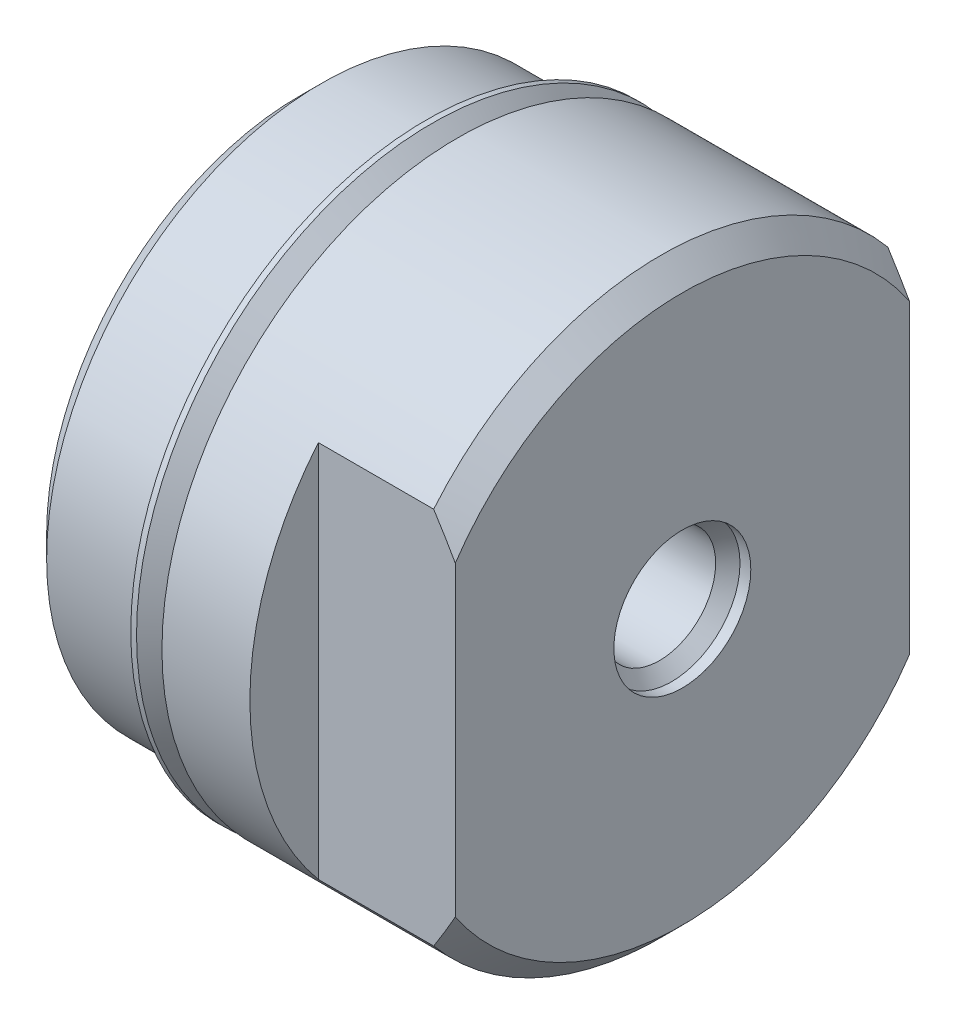
SolidWorks part; units mm, degrees
material "AISI 304"
ref_plane "Front Plane" through (0, 0, 0) normal (0, 0, 1) x (1, 0, 0)
ref_plane "Top Plane" through (0, 0, 0) normal (0, 1, 0) x (1, 0, 0)
ref_plane "Right Plane" through (0, 0, 0) normal (1, 0, 0) x (0, 0, -1)
sketch "Sketch1" plane through (0, 0, 0) normal (0, 0, 1) x (1, 0, 0)
  line L0 (0, 0) -> (0, 8.9154)
  line L1 (0, 8.9154) -> (0.762, 9.6774)
  line L2 (0.762, 9.6774) -> (4.0386, 9.6774)
  line L3 (4.0386, 9.6774) -> (4.8006, 8.9154)
  line L4 (4.8006, 8.9154) -> (5.5626, 8.9154)
  line L5 (5.5626, 8.9154) -> (5.5626, 10.414)
  line L6 (5.5626, 10.414) -> (12.7254, 10.414)
  line L7 (12.7254, 10.414) -> (13.4874, 9.652)
  line L8 (13.4874, 9.652) -> (13.4874, 0)
  line L9 (13.4874, 0) -> (0, 0)
  line L10 (13.4874, 0) -> (0, 0) construction
revolve "Revolve1" add sketch "Sketch1" angle 360 about L10 reverse direction yes
ref_plane "Plane1" through (13.4874, 0, 0) normal (1, 0, 0) x (0, 0, -1)
sketch "Sketch2" plane through (13.4874, 0, 0) normal (1, 0, 0) x (0, 0, -1)
  line L0 (-16.002, -41.656) -> (16.002, -41.656)
  line L1 (16.002, -41.656) -> (16.002, 41.656)
  line L2 (16.002, 41.656) -> (-16.002, 41.656)
  line L3 (-16.002, 41.656) -> (-16.002, -41.656)
  line L4 (-8.001, -20.828) -> (8.001, -20.828)
  line L5 (8.001, -20.828) -> (8.001, 20.828)
  line L6 (8.001, 20.828) -> (-8.001, 20.828)
  line L7 (-8.001, 20.828) -> (-8.001, -20.828)
extrude "Cut-Extrude1" cut sketch "Sketch2" against normal blind 4.826
hole_wizard "Hole1" positions "Sketch4" profile "Sketch3" legacy
sketch "Sketch4" plane through (0, 0, 0) normal (-1, 0, 0) x (0, 0, 1)
  point P0 (0, 0)
sketch "Sketch3" plane through (0, 0, 0) normal (0, 1, 0) x (0, 0, 1)
  line L0 (0, 0) -> (0, 6.35)
  line L1 (0, 6.35) -> (6.35, 6.35)
  line L2 (6.35, 6.35) -> (6.35, 0.254)
  line L3 (6.35, 0.254) -> (6.604, 0)
  line L4 (6.604, 0) -> (0, 0)
  line L5 (0, -6.4453) -> (0, 115.525) construction
  line L6 (-6.35, 0.254) -> (-6.604, 0) construction
  dimension "Diameter" = 12.7
  dimension "Depth" = 6.35
  dimension "C-Sink Angle" = 90
  dimension "C-Sink Diameter" = 13.208
hole_wizard "Hole2" positions "Sketch6" profile "Sketch5" legacy
sketch "Sketch6" plane through (13.4874, 0, 0) normal (1, 0, 0) x (0, 0, -1)
  point P0 (0, 0)
sketch "Sketch5" plane through (13.4874, 0, 0) normal (0, 1, 0) x (0, 0, -1)
  line L0 (0, 0) -> (0, 13.8684)
  line L1 (0, 13.8684) -> (1.9837, 13.8684)
  line L2 (1.9837, 13.8684) -> (1.9837, 0.8103)
  line L3 (1.9837, 0.8103) -> (2.413, 0.381)
  line L4 (2.413, 0.381) -> (2.413, 0)
  line L5 (2.413, 0) -> (0, 0)
  line L6 (0, -6.13) -> (0, 109.2824) construction
  line L7 (-1.9837, 0.8103) -> (-2.413, 0.381) construction
  line L8 (0, 13.8684) -> (-1.9837, 13.8684) construction
  dimension "Diameter" = 3.9675
  dimension "Depth" = 13.8684
  dimension "C-Drill Diameter" = 4.826
  dimension "C-Drill Depth" = 0.381
  dimension "C-Drill Angle" = 90
cosmetic thread "Cosmetic Thread1" parameters "D1"=7.1374, "D2"=4.826
sketch "Sketch7" plane through (0, 0, 0) normal (0, 0, 1) x (1, 0, 0)
  line L0 (4.4638, 10.3298) -> (5.8782, 8.9154)
  line L1 (5.8782, 8.9154) -> (6.1656, 8.9154)
  line L2 (6.1656, 8.9154) -> (4.667, 10.414)
  line L3 (4.667, 10.414) -> (4.4638, 10.414)
  line L4 (4.4638, 10.414) -> (4.4638, 10.3298)
  line L5 (13.4874, 0) -> (-13.4874, 0) construction
revolve "Revolve2" add sketch "Sketch7" angle 360 about L5 reverse direction yes
ref_plane "Plane2" through (13.4874, 0, 0) normal (1, 0, 0) x (0, 0, -1)
ref_plane "Plane3" through (4.0386, 0, 0) normal (1, 0, 0) x (0, 0, -1)
ref_plane "Plane4" through (0, 0, 0) normal (0, 1, 0) x (1, 0, 0)
ref_plane "Plane5" through (0, 0, 0) normal (0, 0, 1) x (1, 0, 0)
ref_plane "Plane6" through (0, 0, 0) normal (0, 0, 1) x (1, 0, 0)
ref_plane "Plane7" through (0, 0, 0) normal (0, 1, 0) x (1, 0, 0)
ref_plane "Plane8" through (13.4874, 0, 0) normal (1, 0, 0) x (0, 0, -1)
ref_plane "Plane9" through (13.4874, 0, 0) normal (1, 0, 0) x (0, 0, -1)
ref_plane "Plane10" through (13.4874, 0, 0) normal (1, 0, 0) x (0, 0, -1)
ref_plane "a1 XY" through (0, 0, 0) normal (0, 1, 0) x (1, 0, 0)
ref_plane "a1 XZ" through (0, 0, -10.414) normal (0, 0, 1) x (1, 0, 0)
ref_plane "a1 YZ" through (13.4874, 0, 0) normal (1, 0, 0) x (0, 0, -1)
ref_axis "a1 X" through (-80.9, 0, -10.414) along (1, 0, 0)
ref_axis "a1 Y" through (13.4874, 0, 50) along (0, 0, -1)
ref_axis "a1 Z" through (13.4874, 50, -10.414) along (0, -1, 0)
sketch3d "a1"
  point P0 (13.4874, 0, -10.414)
ref_plane "a2 XY" through (0, 0, 0) normal (0, 1, 0) x (1, 0, 0)
ref_plane "a2 XZ" through (0, 0, 10.414) normal (0, 0, 1) x (1, 0, 0)
ref_plane "a2 YZ" through (13.4874, 0, 0) normal (1, 0, 0) x (0, 0, -1)
ref_axis "a2 X" through (-80.9, 0, 10.414) along (1, 0, 0)
ref_axis "a2 Y" through (13.4874, 0, 50) along (0, 0, -1)
ref_axis "a2 Z" through (13.4874, 50, 10.414) along (0, -1, 0)
sketch3d "a2"
  point P0 (13.4874, 0, 10.414)
ref_plane "aa2 XY" through (0, 0, 0) normal (0, 1, 0) x (1, 0, 0)
ref_plane "aa2 XZ" through (0, 0, 0) normal (0, 0, 1) x (1, 0, 0)
ref_plane "aa2 YZ" through (13.4874, 0, 0) normal (1, 0, 0) x (0, 0, -1)
ref_axis "aa2 X" through (-80.9, 0, 0) along (1, 0, 0)
ref_axis "aa2 Y" through (13.4874, 0, 50) along (0, 0, -1)
ref_axis "aa2 Z" through (13.4874, 50, 0) along (0, -1, 0)
sketch3d "aa2"
  point P0 (13.4874, 0, 0)
ref_plane "g1 XY" through (0, 0, 0) normal (0, 1, 0) x (1, 0, 0)
ref_plane "g1 XZ" through (0, 0, 0) normal (0, 0, 1) x (1, 0, 0)
ref_plane "g1 YZ" through (13.4874, 0, 0) normal (1, 0, 0) x (0, 0, -1)
ref_axis "g1 X" through (-80.9, 0, 0) along (1, 0, 0)
ref_axis "g1 Y" through (13.4874, 0, 50) along (0, 0, -1)
ref_axis "g1 Z" through (13.4874, 50, 0) along (0, -1, 0)
sketch3d "g1"
  point P0 (13.4874, 0, 0)
ref_plane "g2 XY" through (0, 0, 0) normal (0, 1, 0) x (1, 0, 0)
ref_plane "g2 XZ" through (0, 0, 0) normal (0, 0, 1) x (1, 0, 0)
ref_plane "g2 YZ" through (8.6614, 0, 0) normal (1, 0, 0) x (0, 0, -1)
ref_axis "g2 X" through (-80.9, 0, 0) along (1, 0, 0)
ref_axis "g2 Y" through (8.6614, 0, 50) along (0, 0, -1)
ref_axis "g2 Z" through (8.6614, 50, 0) along (0, -1, 0)
sketch3d "g2"
  point P0 (8.6614, 0, 0)
ref_plane "k1 XY" through (13.4874, 0, 0) normal (1, 0, 0) x (0, 0, -1)
ref_plane "k1 XZ" through (0, 0, 0) normal (0, -1, 0) x (-1, 0, 0)
ref_plane "k1 YZ" through (0, 0, 8.001) normal (0, 0, -1) x (-1, 0, 0)
ref_axis "k1 X" through (13.4874, 0, 80.9) along (0, 0, -1)
ref_axis "k1 Y" through (13.4874, -50, 8.001) along (0, 1, 0)
ref_axis "k1 Z" through (80.9, 0, 8.001) along (-1, 0, 0)
sketch3d "k1"
  point P0 (13.4874, 0, 8.001)
ref_plane "k2 XY" through (13.4874, 0, 0) normal (1, 0, 0) x (0, 0, -1)
ref_plane "k2 XZ" through (0, 0, 0) normal (0, -1, 0) x (-1, 0, 0)
ref_plane "k2 YZ" through (0, 0, -8.001) normal (0, 0, -1) x (-1, 0, 0)
ref_axis "k2 X" through (13.4874, 0, 80.9) along (0, 0, -1)
ref_axis "k2 Y" through (13.4874, -50, -8.001) along (0, 1, 0)
ref_axis "k2 Z" through (80.9, 0, -8.001) along (-1, 0, 0)
sketch3d "k2"
  point P0 (13.4874, 0, -8.001)
ref_plane "l1 XY" through (0, 0, 0) normal (0, 1, 0) x (1, 0, 0)
ref_plane "l1 XZ" through (0, 0, 0) normal (0, 0, 1) x (1, 0, 0)
ref_plane "l1 YZ" through (13.4874, 0, 0) normal (1, 0, 0) x (0, 0, -1)
ref_axis "l1 X" through (-80.9, 0, 0) along (1, 0, 0)
ref_axis "l1 Y" through (13.4874, 0, 50) along (0, 0, -1)
ref_axis "l1 Z" through (13.4874, 50, 0) along (0, -1, 0)
sketch3d "l1"
  point P0 (13.4874, 0, 0)
ref_plane "rear head XY" through (4.0386, 0, 0) normal (1, 0, 0) x (0, 0, -1)
ref_plane "rear head XZ" through (0, 0, 0) normal (0, -1, 0) x (-1, 0, 0)
ref_plane "rear head YZ" through (0, 0, 0) normal (0, 0, -1) x (-1, 0, 0)
ref_axis "rear head X" through (4.0386, 0, 80.9) along (0, 0, -1)
ref_axis "rear head Y" through (4.0386, -50, 0) along (0, 1, 0)
ref_axis "rear head Z" through (80.9, 0, 0) along (-1, 0, 0)
sketch3d "rear head"
  point P0 (4.0386, 0, 0)
ref_plane "rod XY" through (0, 0, 0) normal (1, 0, 0) x (0, 0, -1)
ref_plane "rod XZ" through (0, 0, 0) normal (0, -1, 0) x (-1, 0, 0)
ref_plane "rod YZ" through (0, 0, 0) normal (0, 0, -1) x (-1, 0, 0)
ref_axis "rod X" through (0, 0, 80.9) along (0, 0, -1)
ref_axis "rod Y" through (0, -50, 0) along (0, 1, 0)
ref_axis "rod Z" through (80.9, 0, 0) along (-1, 0, 0)
sketch3d "rod"
  point P0 (0, 0, 0)
ref_plane "st XY" through (13.4874, 0, 0) normal (1, 0, 0) x (0, 0, -1)
ref_plane "st XZ" through (0, -10.414, 0) normal (0, -1, 0) x (-1, 0, 0)
ref_plane "st YZ" through (0, 0, 0) normal (0, 0, -1) x (-1, 0, 0)
ref_axis "st X" through (13.4874, -10.414, 80.9) along (0, 0, -1)
ref_axis "st Y" through (13.4874, -50, 0) along (0, 1, 0)
ref_axis "st Z" through (80.9, -10.414, 0) along (-1, 0, 0)
sketch3d "st"
  point P0 (13.4874, -10.414, 0)
ref_plane "st1 XY" through (13.4874, 0, 0) normal (1, 0, 0) x (0, 0, -1)
ref_plane "st1 XZ" through (0, -10.414, 0) normal (0, -1, 0) x (-1, 0, 0)
ref_plane "st1 YZ" through (0, 0, 0) normal (0, 0, -1) x (-1, 0, 0)
ref_axis "st1 X" through (13.4874, -10.414, 80.9) along (0, 0, -1)
ref_axis "st1 Y" through (13.4874, -50, 0) along (0, 1, 0)
ref_axis "st1 Z" through (80.9, -10.414, 0) along (-1, 0, 0)
sketch3d "st1"
  point P0 (13.4874, -10.414, 0)
ref_plane "to fb r XY" through (13.4874, 0, 0) normal (1, 0, 0) x (0, 0, -1)
ref_plane "to fb r XZ" through (0, 0, 0) normal (0, -1, 0) x (-1, 0, 0)
ref_plane "to fb r YZ" through (0, 0, 0) normal (0, 0, -1) x (-1, 0, 0)
ref_axis "to fb r X" through (13.4874, 0, 80.9) along (0, 0, -1)
ref_axis "to fb r Y" through (13.4874, -50, 0) along (0, 1, 0)
ref_axis "to fb r Z" through (80.9, 0, 0) along (-1, 0, 0)
sketch3d "to fb r"
  point P0 (13.4874, 0, 0)
ref_plane "to pivot bracket XY" through (0, 0, 0) normal (0, 0, 1) x (1, 0, 0)
ref_plane "to pivot bracket XZ" through (0, 0, 0) normal (0, -1, 0) x (-1, 0, 0)
ref_plane "to pivot bracket YZ" through (0, 0, 0) normal (1, 0, 0) x (0, 0, -1)
ref_axis "to pivot bracket X" through (-80.9, 0, 0) along (1, 0, 0)
ref_axis "to pivot bracket Y" through (0, -50, 0) along (0, 1, 0)
ref_axis "to pivot bracket Z" through (0, 0, 80.9) along (0, 0, -1)
sketch3d "to pivot bracket"
  point P0 (0, 0, 0)
ref_plane "to pivot bracket1 XY" through (0, 0, 0) normal (0, 1, 0) x (1, 0, 0)
ref_plane "to pivot bracket1 XZ" through (0, 0, 0) normal (0, 0, 1) x (1, 0, 0)
ref_plane "to pivot bracket1 YZ" through (0, 0, 0) normal (1, 0, 0) x (0, 0, -1)
ref_axis "to pivot bracket1 X" through (-80.9, 0, 0) along (1, 0, 0)
ref_axis "to pivot bracket1 Y" through (0, 0, 50) along (0, 0, -1)
ref_axis "to pivot bracket1 Z" through (0, 50, 0) along (0, -1, 0)
sketch3d "to pivot bracket1"
  point P0 (0, 0, 0)
